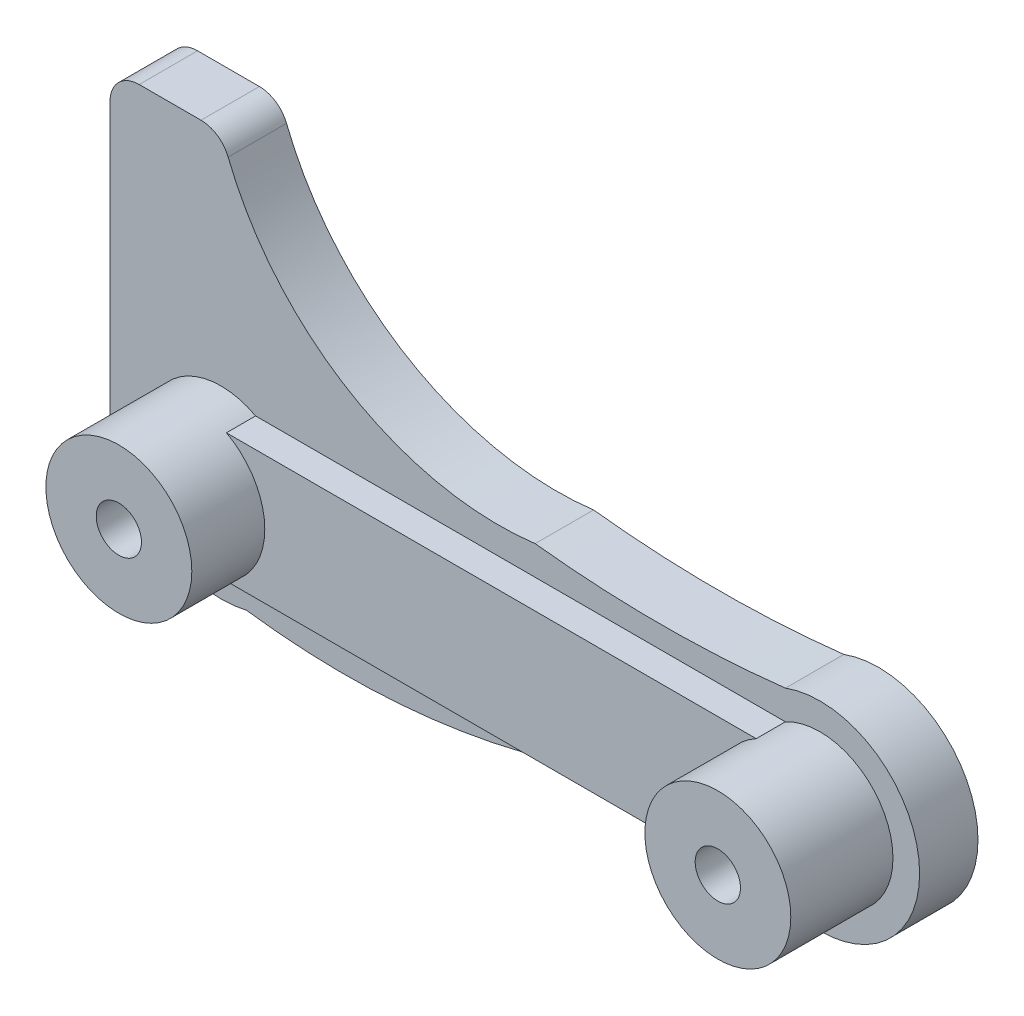
SolidWorks part; units mm, degrees
ref_plane "Plan de face" through (0, 0, 0) normal (0, 0, 1) x (1, 0, 0)
ref_plane "Plan de dessus" through (0, 0, 0) normal (0, 1, 0) x (1, 0, 0)
ref_plane "Plan de droite" through (0, 0, 0) normal (1, 0, 0) x (0, 0, -1)
sketch "Esquisse1" plane through (0, 0, 0) normal (0, 0, 1) x (1, 0, 0)
  line L0 (2.3705, 4.4023) -> (38.6705, 4.4023)
  line L1 (14.9398, 0) -> (50014.9398, 0) construction
  line L2 (2.3705, -4.4023) -> (38.6705, -4.4023)
  arc A1 (2.3705, 4.4023) -> (2.3705, -4.4023) centre (0, 0) ccw
  arc A2 (38.6705, -4.4023) -> (38.6705, 4.4023) centre (41.0411, 0) ccw
  dimension "D1" = 10
  dimension "D2" = 10
  dimension "D3" = 36.3
extrude "Boss.-Extru.1" add sketch "Esquisse1" along normal blind 3 and the other way blind 3
sketch "Esquisse2" plane through (0, 0, 3) normal (0, 0, 1) x (1, 0, 0)
  line L0 (0, 0) -> (50000, 0) construction
  circle A0 centre (0, 0) radius 1.55
  circle A2 centre (41.0411, 0) radius 1.55
  arc A3 (38.6705, -4.4023) -> (38.6705, 4.4023) centre (41.0411, 0) ccw construction
  dimension "D1" = 3.1
  dimension "D2" = 3.1
extrude "Enlèv. mat.-Extru.1" cut sketch "Esquisse2" along direction (0, 0, 1) on the side against the normal up to surface (6 mm away) contours A0 | A2 L0 | L0 A2 | L0 A0 region at (41.0411, 0.6578, 3) region at (41.0411, -0.6578, 3) region at (-1.5062, 0, 3) up to face at (20.5205, 0, -3)
sketch "Sketch1" plane through (0, 0, 3) normal (0, 0, 1) x (1, 0, 0)
  circle A0 centre (0, 0) radius 5
  circle A1 centre (0, 0) radius 1.55
  circle A2 centre (41.0411, 0) radius 1.55
  circle A3 centre (41.0411, 0) radius 5
  arc A6 (38.6705, -4.4023) -> (38.6705, 4.4023) centre (41.0411, 0) ccw construction
  arc A7 (2.3705, 4.4023) -> (2.3705, -4.4023) centre (0, 0) ccw construction
extrude "Boss-Extrude1" add sketch "Sketch1" along normal blind 5
ref_plane "Plane1" through (2.3705, 0, 0) normal (1, 0, 0) x (0, 0, -1)
sketch "Sketch3" plane through (0, 0, -3) normal (0, 0, -1) x (-1, 0, 0)
  line L0 (-38.6705, 4.4023) -> (-2.3705, 4.4023)
  line L1 (-38.6705, -4.4023) -> (-2.3705, -4.4023)
  line L2 (-38.6705, 6.4023) -> (49961.3295, 6.4023) construction
  line L3 (-38.6705, 4.4023) -> (-38.6705, 50004.4023) construction
  line L4 (-0.0363, 20.0804) -> (7.6043, 20.0804)
  line L5 (7.6043, 20.0804) -> (7.6043, -0.7845)
  line L6 (-46.1731, -6.4023) -> (49953.8269, -6.4023) construction
  arc A0 (-38.6705, 4.4023) -> (-38.6705, -4.4023) centre (-41.0411, 0) ccw
  arc A1 (-2.3705, 4.4023) -> (-2.3705, -4.4023) centre (0, 0) cw
  arc A2 (-38.6705, 6.4023) -> (-38.6705, -6.4023) centre (-41.0411, 0) ccw
  arc A3 (-38.6705, 6.4023) -> (-21.5269, 6.4023) centre (-30.0987, 81.2104) ccw
  arc A4 (-21.5269, 6.4023) -> (-0.0363, 20.0804) centre (-19.0311, 26.2028) ccw
  arc A5 (7.6043, -0.7845) -> (-1.7434, -7.4433) centre (0, 0) cw
  arc A6 (-38.6705, -6.4023) -> (-20.6429, -6.4023) centre (-29.6567, -67.5907) cw
  arc A7 (-20.6429, -6.4023) -> (-1.7434, -7.4433) centre (-8.4653, 42.6068) ccw
  point P29 (0, 0)
  dimension "D1" = 2
  dimension "D2" = 2
extrude "Boss-Extrude3" add sketch "Sketch3" against normal blind 4
fillet "Fillet1" radius 2 2 edges at (-7.6043, 20.0804, -1) (0.0363, 20.0804, -1)
